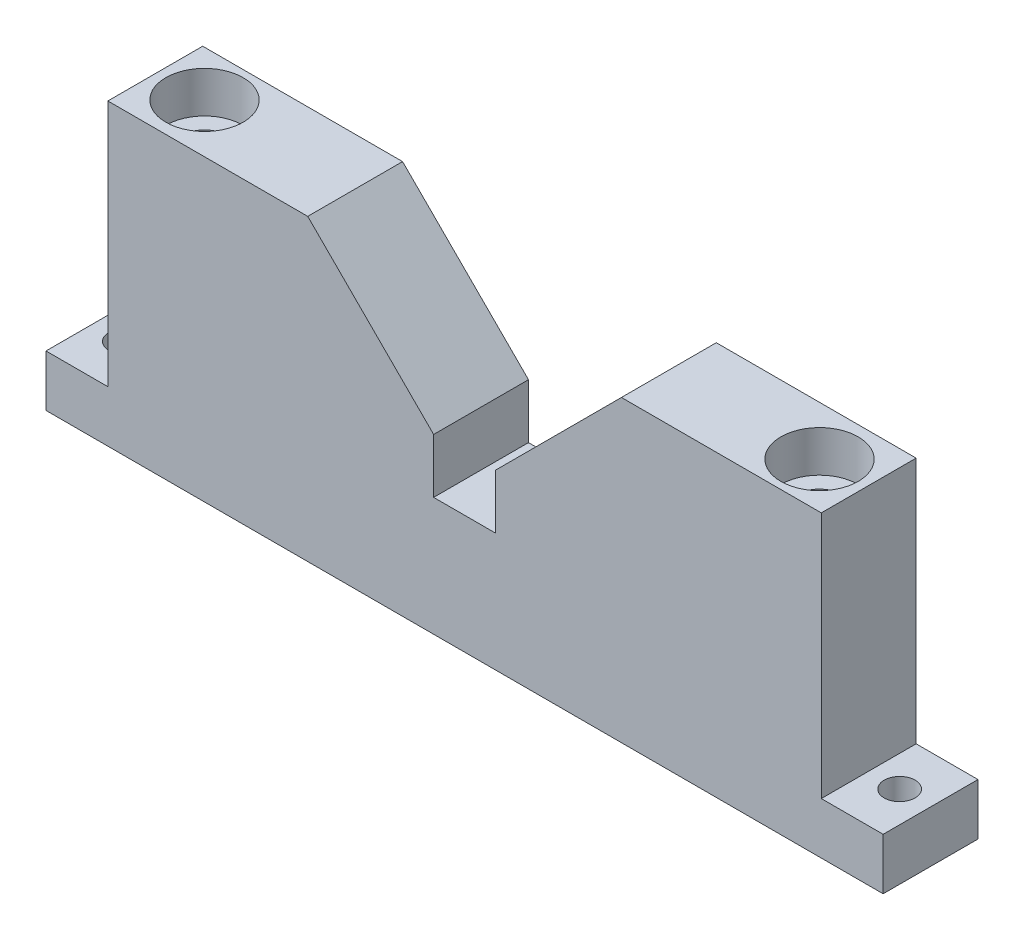
SolidWorks part; units mm, degrees
ref_plane "Спереди" through (0, 0, 0) normal (0, 0, 1) x (1, 0, 0)
ref_plane "Сверху" through (0, 0, 0) normal (0, 1, 0) x (1, 0, 0)
ref_plane "Справа" through (0, 0, 0) normal (1, 0, 0) x (0, 0, -1)
sketch "Эскиз1" plane through (0, 0, 0) normal (0, 0, 1) x (1, 0, 0)
  line L0 (-69.2, -12) -> (-30.4264, -12)
  line L1 (-30.4264, -12) -> (-6, -36.4264)
  line L2 (-6, -36.4264) -> (-6, -47)
  line L3 (-6, -47) -> (6, -47)
  line L4 (6, -47) -> (6, -36.4264)
  line L5 (6, -36.4264) -> (30.4264, -12)
  line L6 (30.4264, -12) -> (69.2, -12)
  line L7 (69.2, -12) -> (69.2, -60)
  line L8 (69.2, -60) -> (-69.2, -60)
  line L9 (-69.2, -60) -> (-69.2, -12)
  circle A0 centre (0, 0) radius 30 construction
  dimension "D1" = 60
  dimension "D3" = 60
  dimension "D2" = 12
  dimension "D4" = 138.4
  dimension "D5" = 12
  dimension "D6" = 35
extrude "Бобышка-Вытянуть1" add sketch "Эскиз1" along normal mid plane 18.4
sketch "Эскиз2" plane through (0, -60, 0) normal (0, -1, 0) x (1, 0, 0)
  line L0 (-81.2, -9.2) -> (81.2, 9.2) construction
  line L1 (-81.2, 9.2) -> (81.2, 9.2)
  line L2 (-81.2, 9.2) -> (-81.2, -9.2)
  line L3 (-81.2, -9.2) -> (81.2, -9.2)
  line L4 (81.2, 9.2) -> (81.2, -9.2)
  line L6 (-69.2, 9.2) -> (69.2, 9.2) construction
  dimension "D1" = 162.4
extrude "Бобышка-Вытянуть2" add sketch "Эскиз2" along normal blind 10
hole_wizard "Цековка для винта с внутренним шестигранником M82" positions "Эскиз12" profile "Эскиз11" counterbore size "M8" standard "ISO" end condition through all
sketch "Эскиз12" plane through (0, -12, 0) normal (0, 1, 0) x (-1, 0, 0)
  line L0 (60, -0.3438) -> (-60, 0.3438) construction
  point P0 (-60, 0.3438)
  point P1 (60, -0.3438)
  dimension "D1" = 120
sketch "Эскиз11" plane through (60, -12, 0.3438) normal (1, 0, 0) x (0, 0, 1)
  line L0 (0, 0) -> (0, 58)
  line L1 (0, 58) -> (4.2, 58)
  line L3 (4.2, 58) -> (4.2, 8)
  line L4 (4.2, 8) -> (7.5, 8)
  line L5 (7.5, 8) -> (7.5, 0)
  line L7 (7.5, 0) -> (0, 0)
  line L11 (0, -6.35) -> (0, 107.95) construction
  dimension "Диаметр сквозного отверстия" = 8.4
  dimension "Глубина сквозного отверстия" = 58
  dimension "Диаметр цековки" = 15
  dimension "Глубина цековки" = 8
hole_wizard "Диаметр отверстия Ø6.0 (6)2" positions "Эскиз14" profile "Эскиз13" hole size "Ø6.0" standard "ISO" end condition through all
sketch "Эскиз14" plane through (0, -60, 0) normal (0, 1, 0) x (-1, 0, 0)
  line L0 (-75.2, 0) -> (75.2, 0) construction
  line L3 (-81.2, -9.2) -> (-81.2, 9.2) construction
  point P0 (-75.2, 0)
  point P1 (75.2, 0)
  dimension "D1" = 6
sketch "Эскиз13" plane through (75.2, -60, 0) normal (1, 0, 0) x (0, 0, 1)
  line L0 (0, 0) -> (0, 10)
  line L1 (0, 10) -> (3, 10)
  line L2 (3, 10) -> (3, 0)
  line L5 (3, 0) -> (0, 0)
  line L11 (0, -6.35) -> (0, 107.95) construction
  dimension "Диаметр сквозного отверстия" = 6
  dimension "Глубина сквозного отверстия" = 10
ref_plane "mount-plane-1" through (-21.2132, -21.2132, 0) normal (0.7071, 0.7071, 0) x (0.7071, -0.7071, 0)
ref_plane "mount-plane-2" through (21.2132, -21.2132, 0) normal (-0.7071, 0.7071, 0) x (0, 0, 1)
ref_plane "align-plane" through (0, 0, 9.2) normal (0, 0, 1) x (1, 0, 0)
equation "\"D\"= 60"
equation "\"D1@Эскиз1\" = \"D\""
equation "\"D2@Эскиз1\" = \"D\"/5"
equation "\"D3@Эскиз1\" = \"D\""
equation "\"D4@Эскиз1\" = 2*\"D\"+\"Диаметр сквозного отверстия@Эскиз11\"+10"
equation "\"D1@Бобышка-Вытянуть1\" = \"Диаметр сквозного отверстия@Эскиз11\"+10"
equation "\"D1@Эскиз12\" = \"D4@Эскиз1\"- \"Диаметр сквозного отверстия@Эскиз11\"-10"
equation "\"D5@Эскиз1\" = \"D1@Эскиз1\"/5"
equation "\"D6@Эскиз1\" = \"D1@Эскиз1\"/2+5"
equation "\"D1@Эскиз2\" = \"D4@Эскиз1\"+\"Диаметр сквозного отверстия@Эскиз13\"*4"
equation "\"D1@Эскиз14\" = \"Диаметр сквозного отверстия@Эскиз13\""
